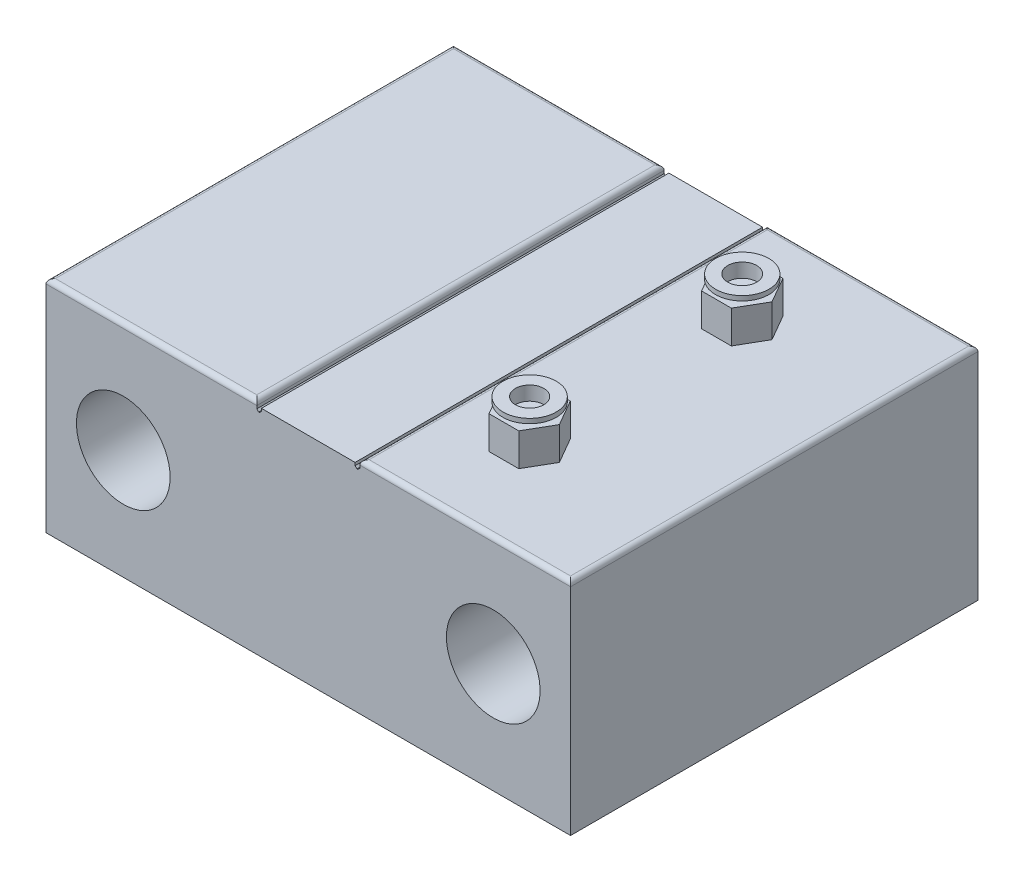
SolidWorks part; units mm, degrees
ref_plane "Alzado" through (0, 0, 0) normal (0, 0, 1) x (1, 0, 0)
ref_plane "Planta" through (0, 0, 0) normal (0, 1, 0) x (1, 0, 0)
ref_plane "Vista lateral" through (0, 0, 0) normal (1, 0, 0) x (0, 0, -1)
sketch "Croquis1" plane through (0, 0, 0) normal (0, 0, 1) x (1, 0, 0)
  line L1 (-56, -23.5) -> (56, -23.5)
  line L2 (-56, -23.5) -> (-56, 23.5)
  line L3 (-56, 23.5) -> (56, 23.5)
  line L4 (56, -23.5) -> (56, 23.5)
  line L5 (-56, -23.5) -> (56, 23.5) construction
  line L6 (-56, 23.5) -> (56, -23.5) construction
  point P0 (0, 0)
  dimension "D1" = 112
  dimension "D2" = 47
extrude "Saliente-Extruir1" add sketch "Croquis1" against normal blind 87
sketch "Croquis2" plane through (0, 0, 0) normal (0, 0, 1) x (1, 0, 0)
  line L0 (-56, 0) -> (-39.5, 0) construction
  line L1 (-56, 23.5) -> (-56, -23.5) construction
  line L2 (0, 23.5) -> (0, -23.5) construction
  line L3 (56, 23.5) -> (-56, 23.5) construction
  line L4 (-56, -23.5) -> (56, -23.5) construction
  circle A0 centre (-39.5, 0) radius 10
  circle A1 centre (39.5, 0) radius 10
  dimension "D2" = 20
  dimension "D1" = 16.5
extrude "Cortar-Extruir1" cut sketch "Croquis2" against normal blind 87
sketch "Croquis4" plane through (0, 0, -87) normal (0, 0, -1) x (-1, 0, 0)
  line L0 (0, 23.5) -> (0, 0) construction
  line L1 (-56, 23.5) -> (56, 23.5) construction
  line L2 (10, 22.5) -> (-10, 22.5)
  line L3 (-10, 22.5) -> (-10, 21.5)
  line L4 (-10, 21.5) -> (-11, 21.5)
  line L5 (-11, 21.5) -> (-11, 23.5)
  line L6 (11, 21.5) -> (11, 23.5)
  line L7 (10, 21.5) -> (11, 21.5)
  line L8 (10, 22.5) -> (10, 21.5)
  line L9 (-11, 23.5) -> (0, 25.8054)
  line L10 (0, 25.8054) -> (11, 23.5)
  point P14 (0, 22.5)
  dimension "D1" = 1
  dimension "D2" = 1
  dimension "D3" = 1
  dimension "D4" = 10
extrude "Cortar-Extruir2" cut sketch "Croquis4" against normal up to surface (87 mm away) up to face at (29.5, 0, 0)
chamfer "Chaflán1" distance 0.4 angle 45 2 edges at (-10, 21.5, -43.5) (-11, 21.5, -43.5)
chamfer "Chaflán2" distance 0.4 angle 45 2 edges at (11, 21.5, -43.5) (10, 21.5, -43.5)
fillet "Redondeo1" radius 1 6 edges at (-33.5, 23.5, 0) (33.5, 23.5, 0) (33.5, 23.5, -87) (-33.5, 23.5, -87) (-56, 23.5, -43.5) (56, 23.5, -43.5)
fillet "Redondeo2" radius 1 2 edges at (-11, 23.5, -43.5) (11, 23.5, -43.5)
sketch "Croquis5" plane through (0, 23.5, 0) normal (0, 1, 0) x (1, 0, 0)
  line L0 (56, 43.5) -> (0, 43.5) construction
  line L1 (32.8143, 66.1963) -> (29.6388, 71.6963)
  line L2 (29.6388, 71.6963) -> (23.288, 71.6963)
  line L3 (23.288, 71.6963) -> (20.1126, 66.1963)
  line L4 (20.1126, 66.1963) -> (23.288, 60.6963)
  line L5 (23.288, 60.6963) -> (29.6388, 60.6963)
  line L6 (29.6388, 60.6963) -> (32.8143, 66.1963)
  line L7 (56, 87) -> (56, 0) construction
  line L8 (29.6388, 26.3037) -> (32.8143, 20.8037)
  line L9 (23.288, 26.3037) -> (29.6388, 26.3037)
  line L10 (20.1126, 20.8037) -> (23.288, 26.3037)
  line L11 (23.288, 15.3037) -> (20.1126, 20.8037)
  line L12 (29.6388, 15.3037) -> (23.288, 15.3037)
  line L13 (32.8143, 20.8037) -> (29.6388, 15.3037)
  circle A0 centre (26.4634, 66.1963) radius 5.5 construction
  circle A1 centre (26.4634, 20.8037) radius 5.5 construction
  dimension "D1" = 11
extrude "Saliente-Extruir2" add sketch "Croquis5" along normal blind 7
sketch "Croquis6" plane through (0, 30.5, 0) normal (0, 1, 0) x (1, 0, 0)
  line L0 (12, 43.5) -> (31.2595, 43.5) construction
  line L1 (12, 86) -> (12, 1) construction
  circle A0 centre (26.4634, 66.1963) radius 3.4727
  circle A1 centre (26.4634, 20.8037) radius 3.4727
extrude "Saliente-Extruir3" add sketch "Croquis6" along normal blind 1
sketch "Croquis7" plane through (0, 31.5, 0) normal (0, 1, 0) x (1, 0, 0)
  line L0 (12, 43.5) -> (34.7899, 43.5) construction
  line L1 (12, 86) -> (12, 1) construction
  circle A0 centre (26.4634, 20.8037) radius 5.6944
  circle A1 centre (26.4634, 66.1963) radius 5.6944
extrude "Saliente-Extruir4" add sketch "Croquis7" along normal blind 1
sketch "Croquis8" plane through (0, 32.5, 0) normal (0, 1, 0) x (1, 0, 0)
  circle A0 centre (26.4634, 20.8037) radius 3.0336
  circle A1 centre (26.4634, 66.1963) radius 3.0923
extrude "Cortar-Extruir3" cut sketch "Croquis8" against normal blind 3
